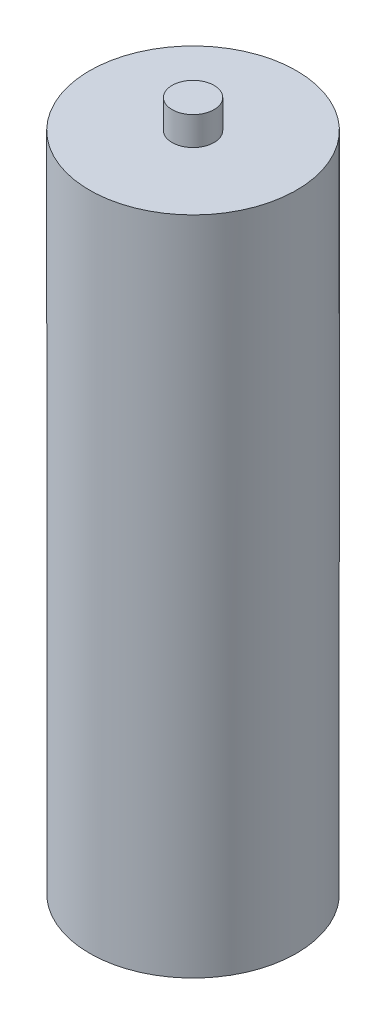
SolidWorks part; units mm, degrees
material "Zinc Alloy 7; AG40B; Zn-4Al-0.015Mg"
ref_plane "Front Plane" through (0, 0, 0) normal (0, 0, 1) x (1, 0, 0)
ref_plane "Top Plane" through (0, 0, 0) normal (0, 1, 0) x (1, 0, 0)
ref_plane "Right Plane" through (0, 0, 0) normal (1, 0, 0) x (0, 0, -1)
sketch "Sketch1" plane through (0, 0, 0) normal (0, 1, 0) x (1, 0, 0)
  circle A0 centre (0, 0) radius 7.25
extrude "Boss-Extrude1" add sketch "Sketch1" along normal blind 46 contours A0
ref_plane "Plane1" through (0, 0.3, 0) normal (0, -1, 0) x (-1, 0, 0)
sketch "Sketch2" plane through (0, 0.3, 0) normal (0, -1, 0) x (-1, 0, 0)
  circle A0 centre (0, 0) radius 7
extrude "Cut-Extrude1" cut sketch "Sketch2" against normal blind 64.5
sketch "Sketch3" plane through (0, 0.3, 0) normal (0, -1, 0) x (-1, 0, 0)
  circle A0 centre (0, 0) radius 6.3062
sketch "Sketch4" plane through (0, 0.3, 0) normal (0, -1, 0) x (-1, 0, 0)
  circle A0 centre (0, 0) radius 7.25
extrude "Boss-Extrude2" add sketch "Sketch4" against normal blind 46
ref_plane "Plane2" through (0, -18.2, 0) normal (0, 1, 0) x (1, 0, 0)
sketch "Sketch5" plane through (0, -18.2, 0) normal (0, 1, 0) x (1, 0, 0)
  circle A0 centre (0, 0) radius 4.7653
ref_plane "Plane3" through (0, 46.3, 0) normal (0, 1, 0) x (1, 0, 0)
sketch "Sketch6" plane through (0, 46.3, 0) normal (0, 1, 0) x (1, 0, 0)
  circle A0 centre (0, 0) radius 1.4713
extrude "Boss-Extrude3" add sketch "Sketch6" along normal blind 2
